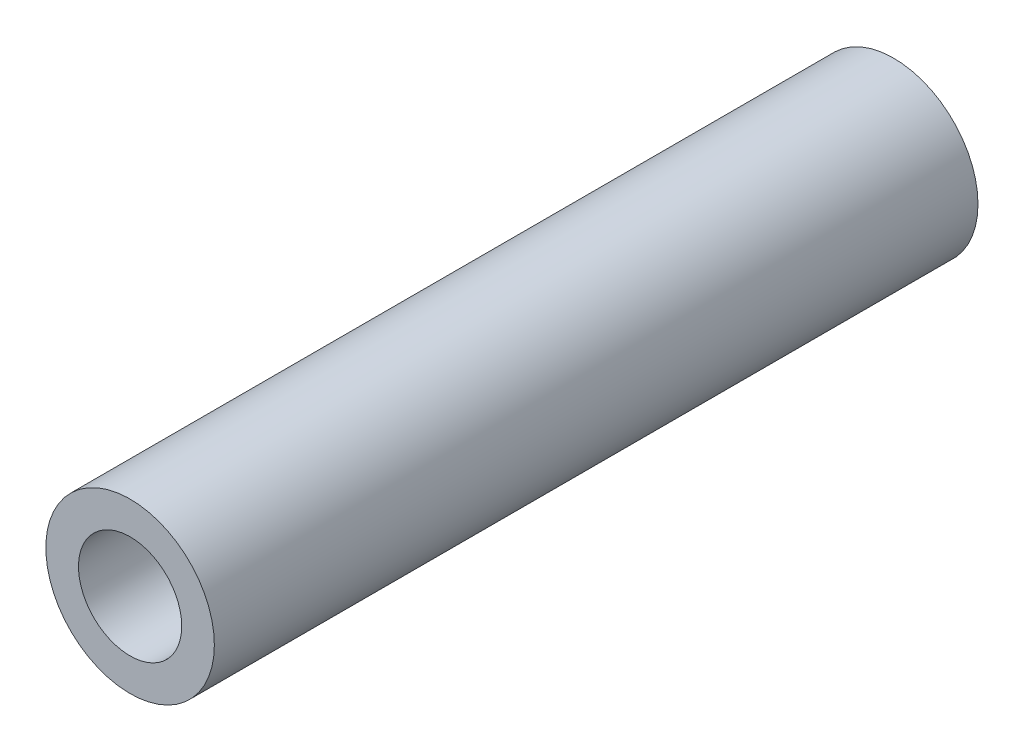
SolidWorks part; units mm, degrees
material "6061-T6 (SS)"
ref_plane "Front Plane" through (0, 0, 0) normal (0, 0, 1) x (1, 0, 0)
ref_plane "Top Plane" through (0, 0, 0) normal (0, 1, 0) x (1, 0, 0)
ref_plane "Right Plane" through (0, 0, 0) normal (1, 0, 0) x (0, 0, -1)
sketch "Sketch1" plane through (0, 0, 0) normal (0, 0, 1) x (1, 0, 0)
  circle A0 centre (0, 0) radius 2.4892
  circle A1 centre (0, 0) radius 4.064
  dimension "D1" = 4.9784
  dimension "D2" = 8.128
extrude "Boss-Extrude1" add sketch "Sketch1" along normal mid plane 36.83
